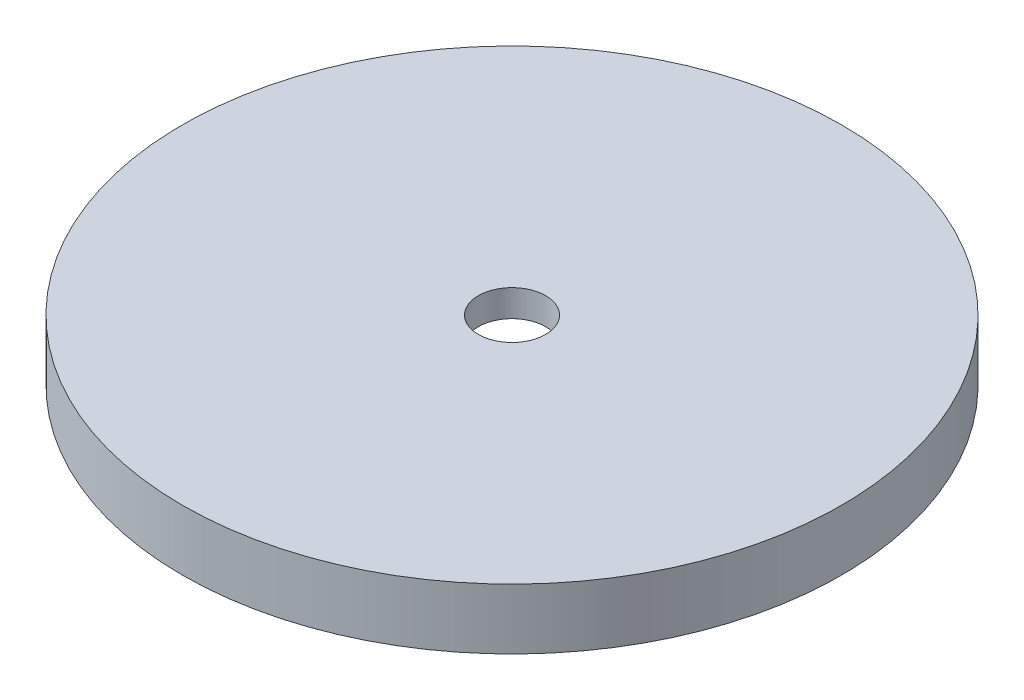
SolidWorks part; units mm, degrees
ref_plane "Front Plane" through (0, 0, 0) normal (0, 0, 1) x (1, 0, 0)
ref_plane "Top Plane" through (0, 0, 0) normal (0, 1, 0) x (1, 0, 0)
ref_plane "Right Plane" through (0, 0, 0) normal (1, 0, 0) x (0, 0, -1)
sketch "Sketch1" plane through (0, 0, 0) normal (0, 1, 0) x (1, 0, 0)
  circle A0 centre (0, 0) radius 18.5
  circle A1 centre (0, 0) radius 24.5
  dimension "D1" = 37
  dimension "D2" = 6
extrude "Boss-Extrude1" add sketch "Sketch1" along normal blind 2.5
sketch "Sketch2" plane through (0, 2.5, 0) normal (0, 1, 0) x (1, 0, 0)
  circle A1 centre (0, 0) radius 24.5
  circle A2 centre (0, 0) radius 24.5
  dimension "D1" = 0
extrude "Boss-Extrude2" add sketch "Sketch2" along normal blind 2
sketch "Sketch3" plane through (0, 0, 0) normal (0, -1, 0) x (1, 0, 0)
  circle A1 centre (0, 0) radius 21.25 construction
  circle A3 centre (0, 0) radius 2.5
  dimension "D1" = 5
  dimension "D2" = 42.5
extrude "Cut-Extrude1" cut sketch "Sketch3" against normal through all
